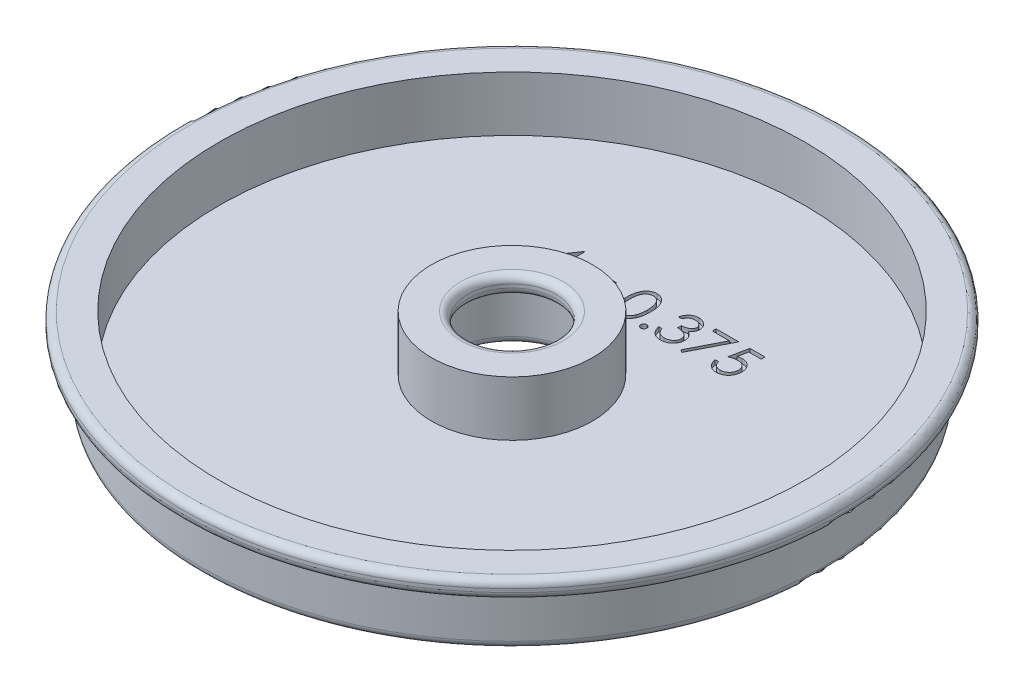
SolidWorks part; units mm, degrees
ref_plane "Front Plane" through (0, 0, 0) normal (0, 0, 1) x (1, 0, 0)
ref_plane "Top Plane" through (0, 0, 0) normal (0, 1, 0) x (1, 0, 0)
ref_plane "Right Plane" through (0, 0, 0) normal (1, 0, 0) x (0, 0, -1)
sketch "Sketch1" plane through (0, 0, 0) normal (0, 0, 1) x (1, 0, 0)
  line L0 (0, 0) -> (0, 11.1543)
  line L3 (13.97, 15.9118) -> (13.97, 6.3868)
  line L4 (13.97, 6.3868) -> (50.8, 6.3868)
  line L5 (50.8, 6.3868) -> (50.8, 15.9118)
  line L8 (52.705, 3.2118) -> (12.065, 3.2118)
  line L9 (53.975, 4.4818) -> (53.975, 11.5037)
  line L10 (55.245, 12.7737) -> (55.88, 12.7737)
  line L11 (57.15, 14.0437) -> (57.15, 14.6418)
  line L12 (50.8, 15.9118) -> (55.88, 15.9118)
  line L13 (13.97, 15.9118) -> (8.89, 15.9118)
  line L14 (7.62, 14.6418) -> (7.62, 14.0068)
  line L15 (10.795, 4.4818) -> (10.795, 11.4668)
  line L16 (9.525, 12.7368) -> (8.89, 12.7368)
  arc A0 (55.88, 15.9118) -> (57.15, 14.6418) centre (55.88, 14.6418) cw
  arc A1 (57.15, 14.0437) -> (55.88, 12.7737) centre (55.88, 14.0437) cw
  arc A2 (55.245, 12.7737) -> (53.975, 11.5037) centre (55.245, 11.5037) ccw
  arc A3 (53.975, 4.4818) -> (52.705, 3.2118) centre (52.705, 4.4818) cw
  arc A4 (12.065, 3.2118) -> (10.795, 4.4818) centre (12.065, 4.4818) cw
  arc A5 (10.795, 11.4668) -> (9.525, 12.7368) centre (9.525, 11.4668) ccw
  arc A6 (8.89, 12.7368) -> (7.62, 14.0068) centre (8.89, 14.0068) cw
  arc A7 (7.62, 14.6418) -> (8.89, 15.9118) centre (8.89, 14.6418) cw
  dimension "D10" = 1.27
  dimension "D1" = 3.175
  dimension "D2" = 6.35
  dimension "D3" = 3.175
  dimension "D4" = 6.35
  dimension "D5" = 3.175
  dimension "D6" = 13.97
  dimension "D7" = 50.8
  dimension "D8" = 3.1382
  dimension "D9" = 3.175
  dimension "D11" = 9.525
  dimension "D12" = 9.525
revolve "Revolve2" add sketch "Sketch1" angle 360 about L0 region at (13.4587, 11.1493, 0)
sketch "Sketch2" plane through (0, 6.3868, 0) normal (0, 1, 0) x (1, 0, 0)
  text T0 "4 x 0.375" font "Century Gothic" height in points 24
  point P1 (-15.9556, 18.225)
extrude "Cut-Extrude1" cut sketch "Sketch2" against normal blind 0.7937
